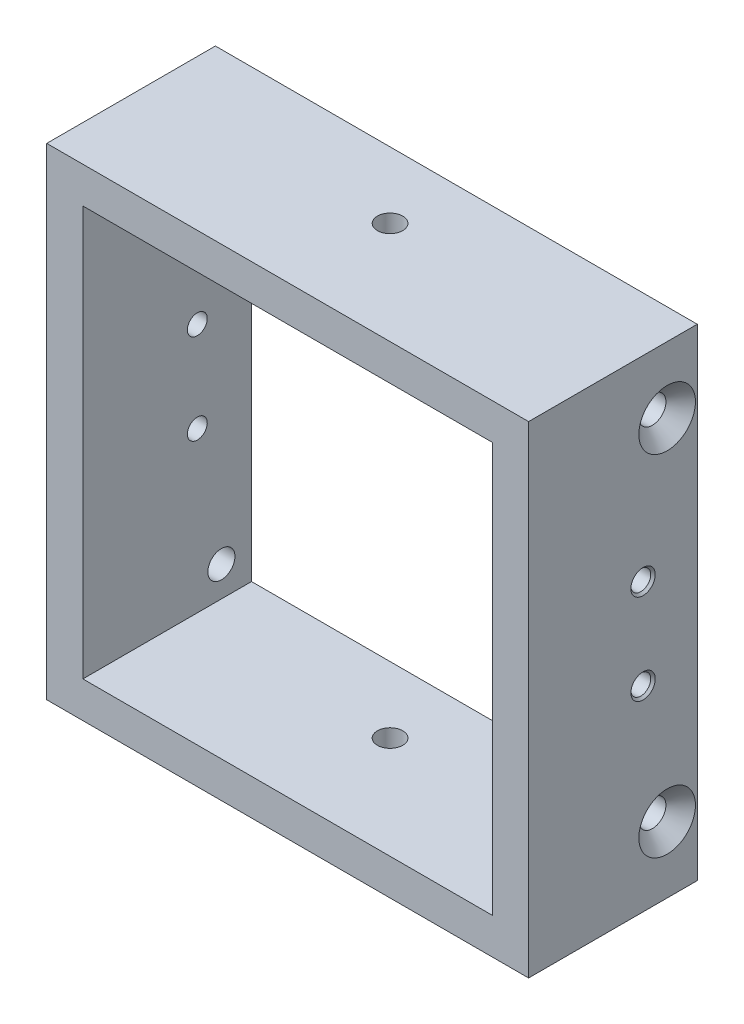
SolidWorks part; units mm, degrees
material "6061-O (SS)"
ref_plane "정면" through (0, 0, 0) normal (0, 0, 1) x (1, 0, 0)
ref_plane "윗면" through (0, 0, 0) normal (0, 1, 0) x (1, 0, 0)
ref_plane "우측면" through (0, 0, 0) normal (1, 0, 0) x (0, 0, -1)
ref_axis "기준축1" through (0, 0, 0) along (0, 0, 1)
sketch "스케치1" plane through (0, 0, 0) normal (0, 0, 1) x (1, 0, 0)
  line L1 (-34, 34) -> (34, 34)
  line L2 (-34, 34) -> (-34, -34)
  line L3 (-34, -34) -> (34, -34)
  line L4 (34, 34) -> (34, -34)
  line L5 (-34, 34) -> (34, -34) construction
  line L6 (-34, -34) -> (34, 34) construction
  line L7 (-40, 40) -> (40, 40)
  line L8 (-40, 40) -> (-40, -40)
  line L9 (-40, -40) -> (40, -40)
  line L10 (40, 40) -> (40, -40)
  line L11 (-40, 40) -> (40, -40) construction
  line L12 (-40, -40) -> (40, 40) construction
  point P0 (0, 0)
  point P6 (0, 0)
  dimension "D1" = 80
  dimension "D2" = 80
  dimension "D3" = 6
  dimension "D4" = 6
extrude "보스-돌출1" add sketch "스케치1" along normal blind 28
hole_wizard "M4 접시 머리 나사용 카운터싱크1" positions "스케치2" profile "스케치3" countersink size "M4" standard "ISO" end condition up to next
sketch "스케치2" plane through (-40, 0, 0) normal (-1, 0, 0) x (0, 0, 1)
  line L1 (28, 34) -> (0, 34) construction
  line L2 (0, 40) -> (0, -40) construction
  point P0 (130.0162, 137.3996)
  point P2 (5, 29)
  point P4 (86.0697, 193.5591)
  dimension "D1" = 5
  dimension "D2" = 5
sketch "스케치3" plane through (-40, 137.3996, 130.0162) normal (0, 1, 0) x (0, 0, 1)
  line L0 (0, 0) -> (0, 80)
  line L1 (0, 80) -> (2.25, 80)
  line L2 (2.25, 80) -> (2.25, 2.45)
  line L3 (2.25, 2.45) -> (4.7, 0)
  line L5 (4.7, 0) -> (0, 0)
  line L6 (-2.25, 2.45) -> (-4.7, 0) construction
  line L11 (0, -6.35) -> (0, 107.95) construction
  dimension "관통 구멍 지름" = 4.5
  dimension "관통 구멍 깊이" = 80
  dimension "표면 카운터싱크 지름" = 9.4
  dimension "표면 카운터싱크 각도" = 90
mirror "대칭 복사1" about plane through (0, 0, 0) normal (0, 1, 0) of "M4 접시 머리 나사용 카운터싱크1"
mirror "대칭 복사2" about plane through (0, 0, 0) normal (1, 0, 0) of "대칭 복사1"
hole_wizard "M4 나사 구멍1" positions "스케치4" profile "스케치5" tap size "M4" standard "ISO" end condition up to next
sketch "스케치4" plane through (-40, 0, 0) normal (-1, 0, 0) x (0, 0, 1)
  line L0 (9, 7.5) -> (9, -7.5)
  line L2 (0, 40) -> (0, -40) construction
  point P0 (9, 7.5)
  point P2 (9, -7.5)
  point P9 (9, 0)
  point P12 (0, 0)
  dimension "D1" = 15
  dimension "D2" = 9
sketch "스케치5" plane through (-40, 7.5, 9) normal (0, 1, 0) x (0, 0, 1)
  line L0 (0, 0) -> (0, 80)
  line L1 (0, 80) -> (1.65, 80)
  line L2 (1.65, 80) -> (1.65, 0.375)
  line L3 (1.65, 0.375) -> (2.025, 0)
  line L5 (2.025, 0) -> (0, 0)
  line L6 (-1.65, 0.375) -> (-2.025, 0) construction
  line L11 (0, -6.35) -> (0, 107.95) construction
  dimension "관통 탭 드릴 지름" = 3.3
  dimension "관통 탭 드릴 깊이" = 80
  dimension "표면 카운터싱크 지름" = 4.05
  dimension "표면 카운터싱크 각도" = 90
cosmetic thread "구멍 나사산1" parameters "D2"=4
cosmetic thread "구멍 나사산2" parameters "D2"=4
mirror "대칭 복사3" about plane through (0, 0, 0) normal (1, 0, 0) of "M4 나사 구멍1"
cosmetic thread "구멍 나사산3" parameters "D2"=4
cosmetic thread "구멍 나사산4" parameters "D2"=4
hole_wizard "M5 나사 구멍1" positions "스케치6" profile "스케치7" tap size "M5" standard "ISO" end condition through all
sketch "스케치6" plane through (0, 40, 0) normal (0, 1, 0) x (1, 0, 0)
  line L0 (40, -28) -> (-40, -28) construction
  point P0 (0, -11)
  dimension "D1" = 17
sketch "스케치7" plane through (0, 40, 11) normal (1, 0, 0) x (0, 0, 1)
  line L0 (0, 0) -> (0, 80)
  line L1 (0, 80) -> (2.1, 80)
  line L2 (2.1, 80) -> (2.1, 0)
  line L5 (2.1, 0) -> (0, 0)
  line L11 (0, -6.35) -> (0, 107.95) construction
  dimension "관통 탭 드릴 지름" = 4.2
  dimension "관통 탭 드릴 깊이" = 80
cosmetic thread "구멍 나사산5" parameters "D2"=5
equation "\"D2@스케치1\"=\"D1@스케치1\""
equation "\"D4@스케치1\"=\"D3@스케치1\""
equation "\"D2@스케치2\"=\"D1@스케치2\""
